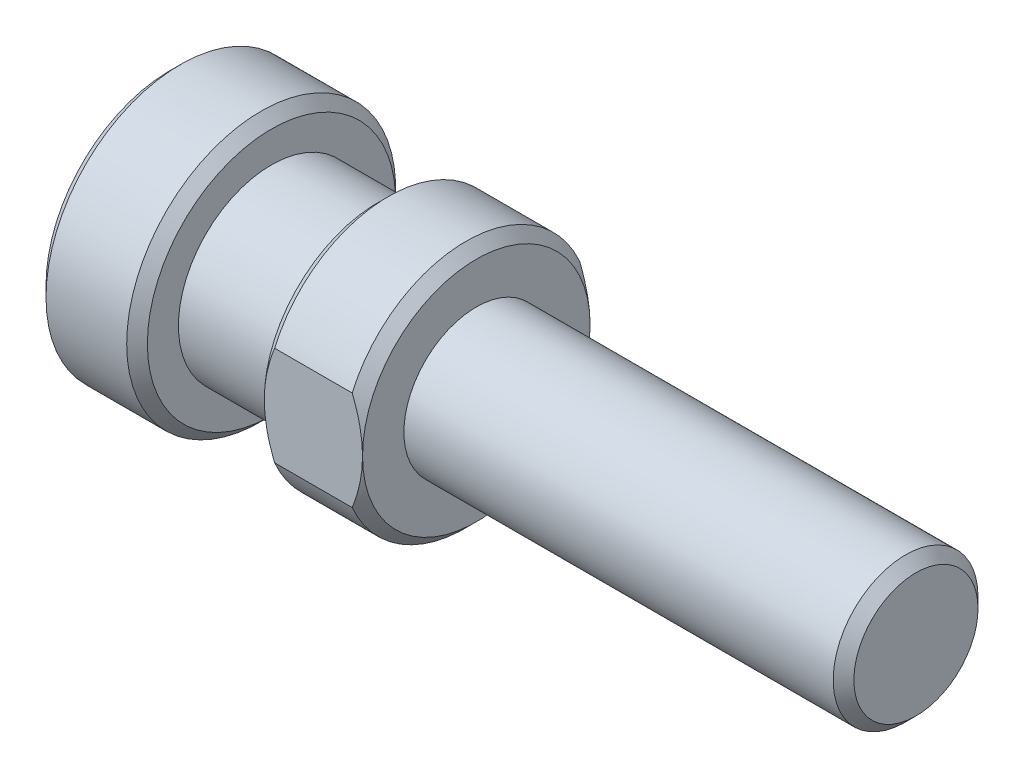
SolidWorks part; units mm, degrees
ref_plane "前基準面" through (0, 0, 0) normal (0, 0, 1) x (1, 0, 0)
ref_plane "上基準面" through (0, 0, 0) normal (0, 1, 0) x (1, 0, 0)
ref_plane "右基準面" through (0, 0, 0) normal (1, 0, 0) x (0, 0, -1)
sketch "草圖1" plane through (0, 0, 0) normal (1, 0, 0) x (0, 0, -1)
  circle A0 centre (0, 0) radius 12
  dimension "D1" = 24
extrude "伸長1" add sketch "草圖1" along normal blind 9.5
sketch "草圖2" plane through (9.5, 0, 0) normal (1, 0, 0) x (0, 0, -1)
  circle A0 centre (0, 0) radius 7
  dimension "D1" = 14
extrude "伸長2" add sketch "草圖2" along normal blind 42.5
cosmetic thread "裝飾螺紋線1" parameters "D2"=11
sketch "草圖3" plane through (0, 0, 0) normal (-1, 0, 0) x (0, 0, 1)
  circle A0 centre (0, 0) radius 9
  dimension "D1" = 18
extrude "伸長3" add sketch "草圖3" along normal blind 10.3
sketch "草圖4" plane through (-10.3, 0, 0) normal (-1, 0, 0) x (0, 0, 1)
  circle A0 centre (0, 0) radius 13
  dimension "D1" = 26
extrude "伸長4" add sketch "草圖4" along normal blind 9.8
sketch "草圖5" plane through (9.5, 0, 0) normal (1, 0, 0) x (0, 0, -1)
  line L0 (0, 0) -> (0, 12) construction
  line L2 (-11, 4.7958) -> (-11, -4.7958)
  line L4 (11, 4.7958) -> (11, -4.7958)
  circle A0 centre (0, 0) radius 12 construction
  arc A1 (-11, 4.7958) -> (-11, -4.7958) centre (0, 0) ccw
  arc A2 (11, -4.7958) -> (11, 4.7958) centre (0, 0) ccw
  dimension "D1" = 22
extrude "除料-伸長3" cut sketch "草圖5" against normal blind 10
chamfer "導角1" distance 1 angle 45 7 edges at (-20.1, 0, 13) (-10.3, 0, 13) (9.5, -12, 0) (0, -12, 0) (0, 12, 0) (9.5, 12, 0) (52, 0, -7)
